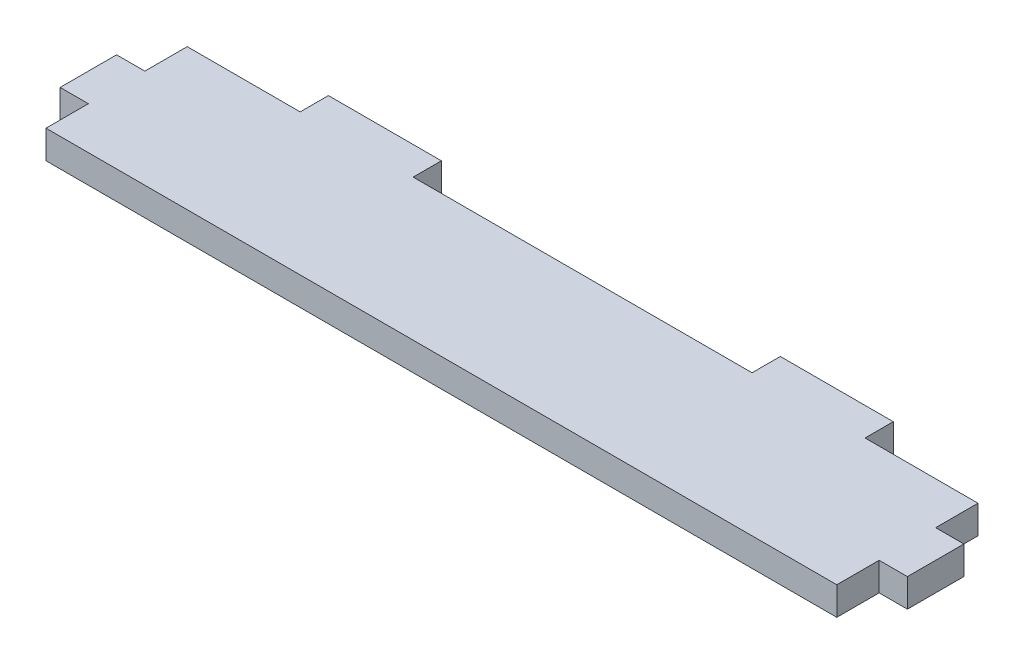
SolidWorks part; units mm, degrees
ref_plane "Front Plane" through (0, 0, 0) normal (0, 0, 1) x (1, 0, 0)
ref_plane "Top Plane" through (0, 0, 0) normal (0, 1, 0) x (1, 0, 0)
ref_plane "Right Plane" through (0, 0, 0) normal (1, 0, 0) x (0, 0, -1)
sketch "Sketch1" plane through (0, 0, 0) normal (0, 1, 0) x (1, 0, 0)
  line L0 (0, 12.5) -> (0, -12.5) construction
  line L1 (-70, 12.5) -> (-50, 12.5)
  line L2 (-70, 12.5) -> (-70, 5)
  line L3 (-70, -12.5) -> (70, -12.5)
  line L4 (70, 12.5) -> (70, 5)
  line L5 (-70, 12.5) -> (70, -12.5) construction
  line L6 (-70, -12.5) -> (70, 12.5) construction
  line L7 (-50, 12.5) -> (-30, 12.5) construction
  line L8 (-50, 12.5) -> (-50, 17.5)
  line L9 (-50, 17.5) -> (-30, 17.5)
  line L10 (-30, 12.5) -> (-30, 17.5)
  line L11 (50, 17.5) -> (30, 17.5)
  line L12 (30, 12.5) -> (30, 17.5)
  line L13 (50, 12.5) -> (30, 12.5) construction
  line L14 (50, 12.5) -> (50, 17.5)
  line L15 (-50, 12.5) -> (-30, 12.5) construction
  line L16 (-30, 12.5) -> (30, 12.5)
  line L17 (30, 12.5) -> (50, 12.5) construction
  line L18 (50, 12.5) -> (70, 12.5)
  line L19 (75, -5) -> (70, -5)
  line L20 (-75, 5) -> (-70, 5)
  line L21 (-75, 5) -> (-75, -5)
  line L22 (-75, -5) -> (-70, -5)
  line L23 (-70, 5) -> (-70, -5) construction
  line L24 (-75, 5) -> (-70, -5) construction
  line L25 (-75, -5) -> (-70, 5) construction
  line L26 (70, 5) -> (70, -5) construction
  line L27 (75, 5) -> (70, 5)
  line L28 (75, 5) -> (75, -5)
  line L29 (-70, 5) -> (-70, -5) construction
  line L30 (-70, -5) -> (-70, -12.5)
  line L31 (70, 5) -> (70, -5) construction
  line L32 (70, -5) -> (70, -12.5)
  point P0 (0, 0)
  point P16 (0, 0)
  point P17 (-72.5, 0)
  dimension "D1" = 140
  dimension "D2" = 25
  dimension "D3" = 5
  dimension "D4" = 20
  dimension "D5" = 20
  dimension "D6" = 5
  dimension "D7" = 10
extrude "Boss-Extrude1" add sketch "Sketch1" along normal blind 5
